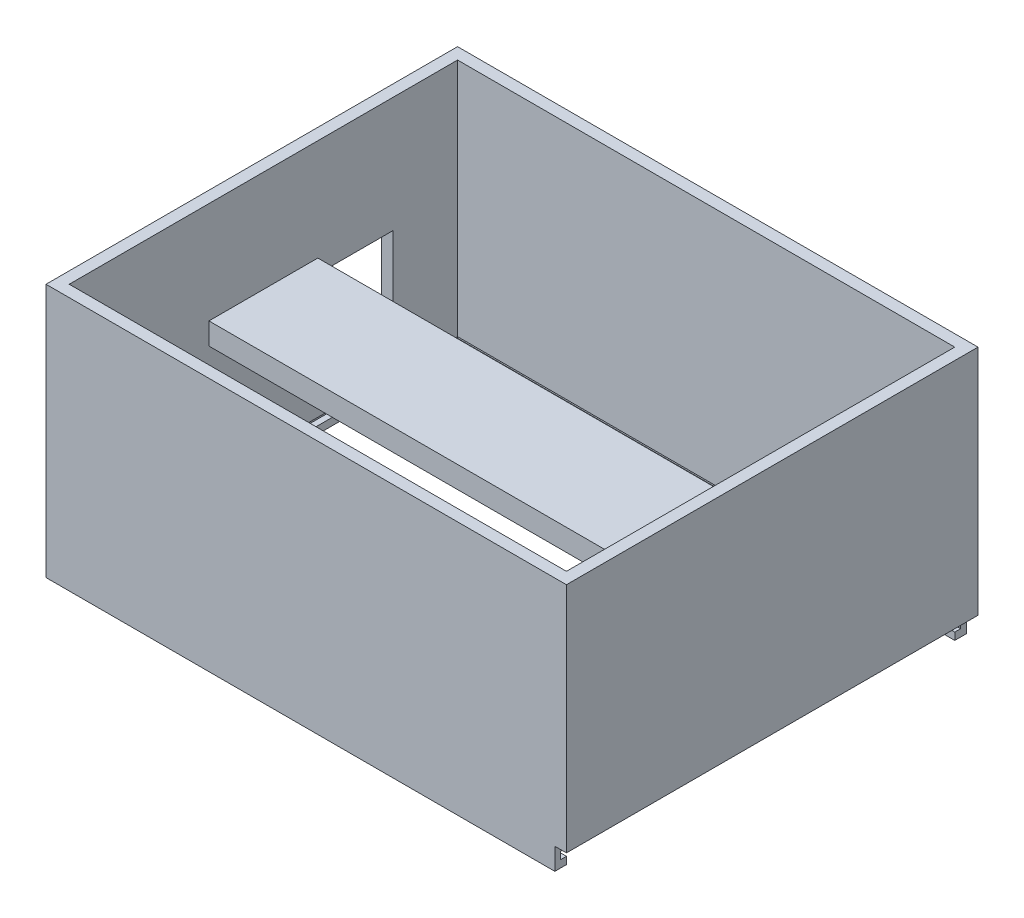
SolidWorks part; units mm, degrees
ref_plane "Front Plane" through (0, 0, 0) normal (0, 0, 1) x (1, 0, 0)
ref_plane "Top Plane" through (0, 0, 0) normal (0, 1, 0) x (1, 0, 0)
ref_plane "Right Plane" through (0, 0, 0) normal (1, 0, 0) x (0, 0, -1)
sketch "Sketch1" plane through (0, 0, 0) normal (0, 1, 0) x (1, 0, 0)
  line L1 (-33.021, -34.9955) -> (35.479, -34.9955)
  line L2 (-33.021, -34.9955) -> (-33.021, 18.5045)
  line L3 (-33.021, 18.5045) -> (35.479, 18.5045)
  line L4 (35.479, -34.9955) -> (35.479, 18.5045)
  line L5 (-34.621, 20.1045) -> (37.079, 20.1045)
  line L6 (-34.621, 20.1045) -> (-34.621, -36.5955)
  line L7 (-34.621, -36.5955) -> (37.079, -36.5955)
  line L8 (37.079, 20.1045) -> (37.079, -36.5955)
  dimension "D1" = 53.5
  dimension "D2" = 68.5
  dimension "D3" = 1.6
  dimension "D4" = 1.6
  dimension "D5" = 1.6
  dimension "D6" = 1.6
extrude "Boss-Extrude1" add sketch "Sketch1" along normal blind 32
sketch "Sketch2" plane through (-33.021, 0, 0) normal (1, 0, 0) x (0, 0, -1)
  line L0 (18.5045, 32) -> (-34.9955, 32) construction
  line L1 (-15.7455, 15) -> (-0.7455, 15)
  line L2 (-15.7455, 15) -> (-15.7455, 18)
  line L3 (-15.7455, 18) -> (-0.7455, 18)
  line L4 (-0.7455, 15) -> (-0.7455, 18)
  point P6 (-8.2455, 32)
  dimension "D1" = 14
  dimension "D2" = 15
  dimension "D3" = 3
  dimension "D4" = 7.5
extrude "Boss-Extrude2" add sketch "Sketch2" along normal blind 70
sketch "Sketch3" plane through (-33.021, 0, 0) normal (1, 0, 0) x (0, 0, -1)
  line L0 (18.5045, 32) -> (18.5045, 0) construction
  line L1 (-2.6955, 4.1) -> (9.6045, 4.1)
  line L2 (-2.6955, 4.1) -> (-2.6955, 16.1)
  line L3 (-2.6955, 16.1) -> (9.6045, 16.1)
  line L4 (9.6045, 4.1) -> (9.6045, 16.1)
  line L5 (18.5045, 0) -> (-34.9955, 0) construction
  line L7 (-31.8955, 4.1) -> (-22.5955, 4.1)
  line L8 (-31.8955, 4.1) -> (-31.8955, 15.1)
  line L9 (-31.8955, 15.1) -> (-22.5955, 15.1)
  line L10 (-22.5955, 4.1) -> (-22.5955, 15.1)
  dimension "D1" = 12.3
  dimension "D2" = 12
  dimension "D3" = 8.9
  dimension "D4" = 4.1
  dimension "D5" = 9.3
  dimension "D6" = 11
  dimension "D7" = 19.9
  dimension "D8" = 4.1
extrude "Cut-Extrude1" cut sketch "Sketch3" against normal blind 1.6
extrude "Cut-Extrude2" cut sketch "Sketch3<2>" along normal blind 18
sketch "Sketch3<2>" plane through (-33.021, 0, 0) normal (1, 0, 0) x (0, 0, -1) same geometry as "Sketch3"
sketch "Sketch4" plane through (0, 0, 0) normal (0, -1, 0) x (1, 0, 0)
  line L0 (35.479, 36.5955) -> (35.479, 34.9955)
  line L1 (-34.621, 36.5955) -> (37.079, 36.5955) construction
  line L2 (-33.021, 34.9955) -> (35.479, 34.9955) construction
  line L3 (35.479, 34.9955) -> (-33.021, 34.9955)
  line L4 (-33.021, 34.9955) -> (-33.021, -18.5045)
  line L5 (-33.021, -18.5045) -> (35.479, -18.5045)
  line L6 (35.479, -18.5045) -> (35.479, -20.1045)
  line L7 (37.079, -20.1045) -> (-34.621, -20.1045) construction
  line L8 (35.479, -20.1045) -> (-34.621, -20.1045)
  line L9 (-34.621, -20.1045) -> (-34.621, 36.5955)
  line L10 (-34.621, 36.5955) -> (35.479, 36.5955)
  dimension "D1" = 0
extrude "Boss-Extrude3" add sketch "Sketch4" along normal blind 3
sketch "Sketch5" plane through (35.479, 0, 0) normal (1, 0, 0) x (0, 0, -1)
  line L0 (-34.9955, -3) -> (-36.5955, -3) construction
  line L1 (-35.7955, -1) -> (19.3045, -1)
  line L2 (-35.7955, -1) -> (-35.7955, -2)
  line L3 (-35.7955, -2) -> (19.3045, -2)
  line L4 (19.3045, -1) -> (19.3045, -2)
  line L5 (-34.9955, 0) -> (-36.5955, 0) construction
  line L6 (-36.5955, -3) -> (-36.5955, 0) construction
  line L7 (20.1045, -3) -> (20.1045, 0) construction
  dimension "D1" = 1
  dimension "D2" = 1
  dimension "D3" = 0.8
  dimension "D4" = 0.8
extrude "Cut-Extrude3" cut sketch "Sketch5" against normal blind 69.3
